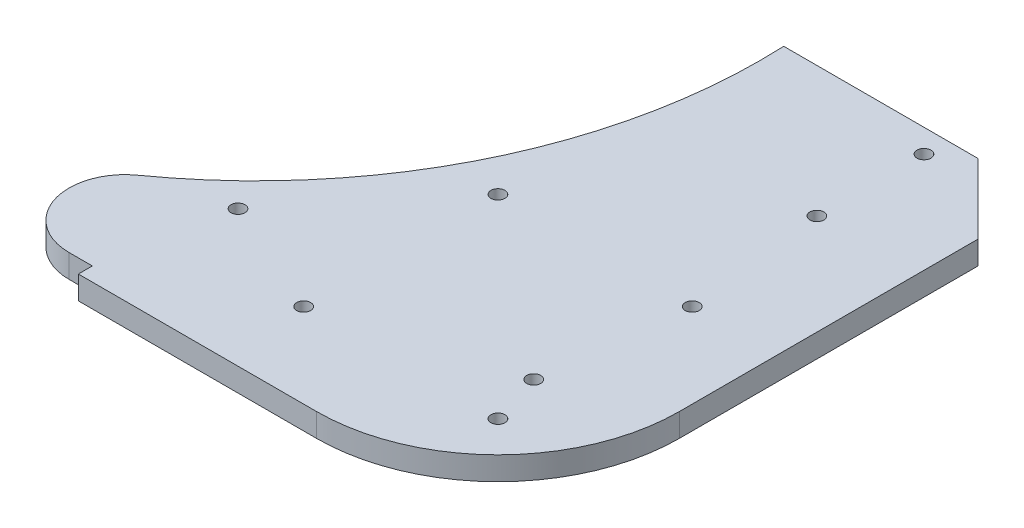
SolidWorks part; units mm, degrees
material "ABS PC"
ref_plane "Plan de face" through (0, 0, 0) normal (0, 0, 1) x (1, 0, 0)
ref_plane "Plan de dessus" through (0, 0, 0) normal (0, 1, 0) x (1, 0, 0)
ref_plane "Plan de droite" through (0, 0, 0) normal (1, 0, 0) x (0, 0, -1)
sketch "Esquisse1" plane through (0, 0, 0) normal (0, 1, 0) x (1, 0, 0)
  line L0 (-56.1, -39) -> (0, -39) construction
  line L1 (39, 0) -> (39, 164.8329) construction
  line L2 (-51.1, -39) -> (0, -39)
  line L3 (39, 0) -> (39, 64.0829)
  line L4 (-51.1, -36) -> (-51.1, -39) construction
  line L5 (-56.1, -36) -> (-51.1, -36) construction
  line L6 (-51.1, -36) -> (-51.1, -39)
  line L7 (-56.1, -36) -> (-51.1, -36)
  line L8 (-17.7153, 79.0829) -> (24, 79.0829)
  line L10 (12.4, 79.0829) -> (22.4, 79.0829) construction
  line L11 (24, 79.0829) -> (39, 64.0829)
  arc A0 (0, -39) -> (39, 0) centre (0, 0) ccw construction
  arc A2 (0, -39) -> (39, 0) centre (0, 0) ccw
  arc A3 (-63.071, -14.2324) -> (-189.129, -14.2324) centre (-126.1, 74.0829) ccw construction
  arc A4 (-63.071, -14.2324) -> (-17.7153, 79.0829) centre (-126.1, 74.0829) ccw
  arc A6 (-63.071, -14.2324) -> (-56.1, -36) centre (-56.1, -24) ccw
  arc A7 (-63.071, -14.2324) -> (-56.1, -36) centre (-56.1, -24) ccw construction
  point P13 (39, 79.0829)
extrude "Boss.-Extru.1" add sketch "Esquisse1" along normal blind 5
sketch "Esquisse2" plane through (0, 0, 0) normal (0, -1, 0) x (1, 0, 0)
  circle A0 centre (20.8597, 20.8597) radius 1.5
  circle A1 centre (20.8597, -20.8597) radius 1.5
  circle A2 centre (-20.8597, -20.8597) radius 1.5
  circle A3 centre (-20.8597, 20.8597) radius 1.5
  circle A4 centre (17.4, -74.0829) radius 1.5
  circle A5 centre (17.4, 9.7171) radius 1.5
  dimension "D1" = 3
extrude "Enlèv. mat.-Extru.1" cut sketch "Esquisse2" against normal through all
sketch "Esquisse3" plane through (0, 5, 0) normal (0, 1, 0) x (1, 0, 0)
  line L0 (17.4, 51.0829) -> (22.4, 51.0829) construction
  line L1 (-46.1, -9.7171) -> (-46.1, -14.7171) construction
  line L2 (22.4, 52.5829) -> (22.4, 49.5829) construction
  line L3 (-44.6, -14.7171) -> (-47.6, -14.7171) construction
  circle A0 centre (17.4, 51.0829) radius 1.5
  circle A1 centre (-46.1, -9.7171) radius 1.5
  dimension "D1" = 3
  dimension "D2" = 5
extrude "Enlèv. mat.-Extru.2" cut sketch "Esquisse3" against normal through all
